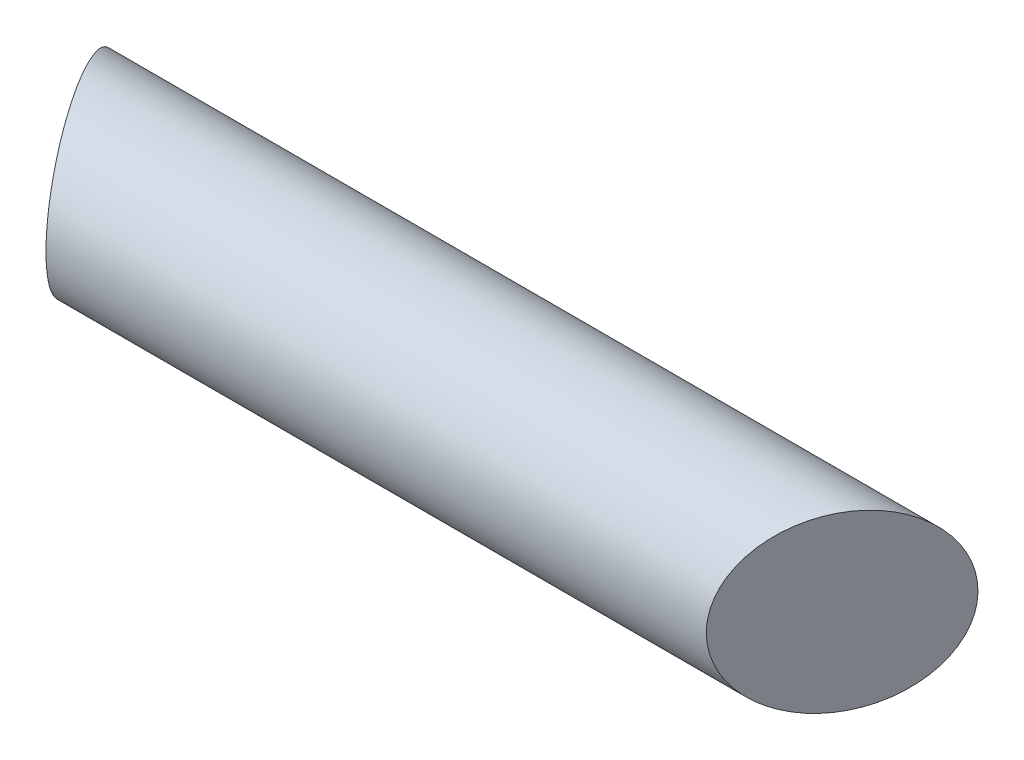
SolidWorks part; units mm, degrees
ref_plane "Front" through (0, 0, 0) normal (0, 0, 1) x (1, 0, 0)
ref_plane "Top" through (0, 0, 0) normal (0, 1, 0) x (1, 0, 0)
ref_plane "Right" through (0, 0, 0) normal (1, 0, 0) x (0, 0, -1)
sketch "草图1" plane through (0, 0, 0) normal (1, 0, 0) x (0, 0, -1)
  circle A0 centre (0, 0) radius 30
  dimension "D1" = 60
extrude "凸台-拉伸1" add sketch "草图1" along normal mid plane 300
ref_plane "基准面1" through (115, 0, 0) normal (1, 0, 0) x (0, 0, -1)
ref_plane "基准面2" through (0, 0, 30) normal (0, 0, 1) x (1, 0, 0)
ref_axis "基准轴1" through (115, 33, 30) along (0, -1, 0)
ref_plane "基准面3" through (99.2404, 0, 57.2965) normal (0.866, 0, 0.5) x (0, -1, 0)
sketch "草图2" plane through (99.2404, 0, 57.2965) normal (0.866, 0, 0.5) x (0, -1, 0)
  line L1 (50.4251, 22.0269) -> (-59.3469, 22.0269)
  line L2 (50.4251, 22.0269) -> (50.4251, 102.2784)
  line L3 (50.4251, 102.2784) -> (-59.3469, 102.2784)
  line L4 (-59.3469, 22.0269) -> (-59.3469, 102.2784)
  line L5 (50.4251, 22.0269) -> (-59.3469, 102.2784) construction
  line L6 (50.4251, 102.2784) -> (-59.3469, 22.0269) construction
  point P0 (-4.4609, 62.1527)
  point P5 (50.4251, 102.2784)
extrude "切除-拉伸1" cut sketch "草图2" along normal through all
mirror "镜向1" about plane through (0, 0, 0) normal (1, 0, 0) of "切除-拉伸1"
